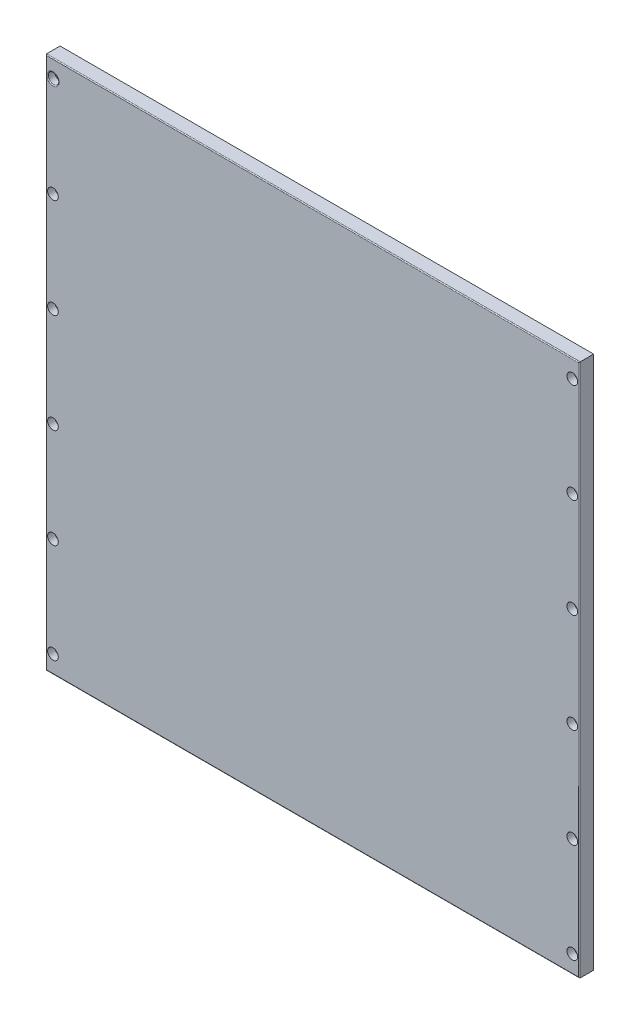
SolidWorks part; units mm, degrees
material "ABS PC"
ref_plane "Front Plane" through (0, 0, 0) normal (0, 0, 1) x (1, 0, 0)
ref_plane "Top Plane" through (0, 0, 0) normal (0, 1, 0) x (1, 0, 0)
ref_plane "Right Plane" through (0, 0, 0) normal (1, 0, 0) x (0, 0, -1)
sketch "Sketch1" plane through (0, 0, 0) normal (0, 0, 1) x (1, 0, 0)
  line L1 (0, 0) -> (300, 0)
  line L2 (0, 0) -> (0, 300)
  line L3 (0, 300) -> (300, 300)
  line L4 (300, 0) -> (300, 300)
extrude "Boss-Extrude1" add sketch "Sketch1" along normal blind 8
sketch "Sketch4" plane through (0, 0, 8) normal (0, 0, 1) x (1, 0, 0)
  line L0 (300, 300) -> (0, 300) construction
  line L1 (0, 300) -> (0, 0) construction
  circle A0 centre (4, 290) radius 3
  dimension "D1" = 10
  dimension "D2" = 4
extrude "Cut-Extrude2" cut sketch "Sketch4" against normal blind 4
sketch "Sketch7" plane through (0, 0, 4) normal (0, 0, 1) x (1, 0, 0)
  circle A0 centre (4, 290) radius 1.5
extrude "Cut-Extrude5" cut sketch "Sketch7" against normal up to next
fillet "Fillet1" radius 0.5 5 edges at (150, 300, 8) (300, 150, 8) (150, 0, 8) (0, 150, 8) (7, 290, 8)
pattern_linear "LPattern1" count 2 spacing 292 along (1, 0, 0) count 6 spacing 56 along (0, -1, 0) of "Cut-Extrude2", "Cut-Extrude5"
